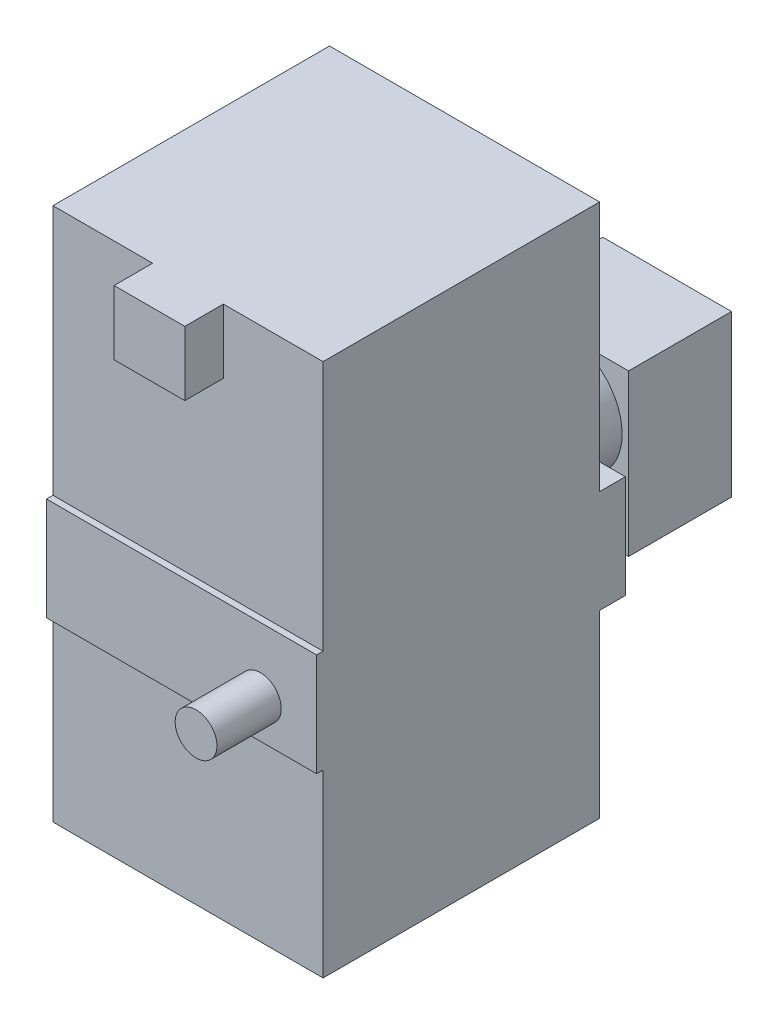
SolidWorks part; units mm, degrees
ref_plane "Alzado" through (0, 0, 0) normal (0, 0, 1) x (1, 0, 0)
ref_plane "Planta" through (0, 0, 0) normal (0, 1, 0) x (1, 0, 0)
ref_plane "Vista lateral" through (0, 0, 0) normal (1, 0, 0) x (0, 0, -1)
sketch "Croquis1" plane through (0, 0, 0) normal (1, 0, 0) x (0, 0, -1)
  line L0 (21.5, 2.5) -> (25.5, 2.5)
  line L1 (21.5, -41.5) -> (-21.5, -41.5)
  line L2 (21.5, -41.5) -> (21.5, -13.5)
  line L3 (21.5, 41.5) -> (-21.5, 41.5)
  line L4 (-21.5, -41.5) -> (-21.5, -13.5)
  line L5 (21.5, -41.5) -> (-21.5, 41.5) construction
  line L6 (21.5, 41.5) -> (-21.5, -41.5) construction
  line L7 (-22.5, -13.5) -> (-21.5, -13.5)
  line L8 (-22.5, -13.5) -> (-22.5, 2.5)
  line L9 (-22.5, 2.5) -> (-21.5, 2.5)
  line L10 (25.5, -13.5) -> (25.5, 2.5)
  line L11 (21.5, 2.5) -> (21.5, 41.5)
  line L12 (21.5, -13.5) -> (25.5, -13.5)
  line L13 (-21.5, 2.5) -> (-21.5, 41.5)
  point P0 (0, 0)
  dimension "D1" = 43
  dimension "D2" = 83
  dimension "D3" = 48
  dimension "D4" = 4
  dimension "D5" = 16
  dimension "D6" = 39
extrude "Saliente-Extruir1" add sketch "Croquis1" along normal blind 42
sketch "Croquis2" plane through (0, 0, 21.5) normal (0, 0, 1) x (1, 0, 0)
  line L0 (42, 41.5) -> (0, 41.5) construction
  line L1 (15.5, 41.5) -> (26.5, 41.5)
  line L2 (15.5, 41.5) -> (15.5, 31.5)
  line L3 (15.5, 31.5) -> (26.5, 31.5)
  line L4 (26.5, 41.5) -> (26.5, 31.5)
  line L5 (15.5, 41.5) -> (0, 41.5) construction
  line L6 (26.5, 41.5) -> (42, 41.5) construction
  dimension "D1" = 10
  dimension "D2" = 11
extrude "Saliente-Extruir2" add sketch "Croquis2" along normal blind 6
sketch "Croquis3" plane through (0, 0, 22.5) normal (0, 0, 1) x (1, 0, 0)
  line L0 (42, 2.5) -> (0, 2.5) construction
  line L1 (42, 2.5) -> (42, -13.5) construction
  circle A0 centre (33.25, -7.5) radius 3.25
  dimension "D1" = 6.5
  dimension "D2" = 10
  dimension "D3" = 8.75
extrude "Saliente-Extruir3" add sketch "Croquis3" along normal blind 10
sketch "Croquis4" plane through (0, 0, -25.5) normal (0, 0, -1) x (-1, 0, 0)
  line L1 (-42, 2.5) -> (0, 2.5) construction
  line L3 (0, -13.5) -> (0, 2.5) construction
  circle A0 centre (-16, -8.5) radius 9
  dimension "D2" = 18
  dimension "D3" = 16
  dimension "D1" = 11
extrude "Saliente-Extruir4" add sketch "Croquis4" along normal blind 16.5
sketch "Croquis5" plane through (0, 0, -42) normal (0, 0, -1) x (-1, 0, 0)
  line L0 (-16, 0.5) -> (-16, -17.5) construction
  line L1 (-26, 0.5) -> (-6, 0.5)
  line L2 (-26, 0.5) -> (-26, -24.5)
  line L3 (-26, -24.5) -> (-6, -24.5)
  line L4 (-6, 0.5) -> (-6, -24.5)
  arc A1 (-8.5167, -13.5) -> (-23.4833, -13.5) centre (-16, -8.5) ccw construction
  circle A2 centre (-16, -8.5) radius 9 construction
  dimension "D1" = 20
  dimension "D2" = 25
extrude "Saliente-Extruir5" add sketch "Croquis5" along normal blind 16
sketch "Croquis6" plane through (0, 0, -58) normal (0, 0, -1) x (-1, 0, 0)
  circle A0 centre (-16, -8.5) radius 3.5
  dimension "D1" = 7
extrude "Saliente-Extruir6" add sketch "Croquis6" along normal blind 1
fillet "Redondeo2" radius 4 1 edges at (12.5, -8.5, -59)
